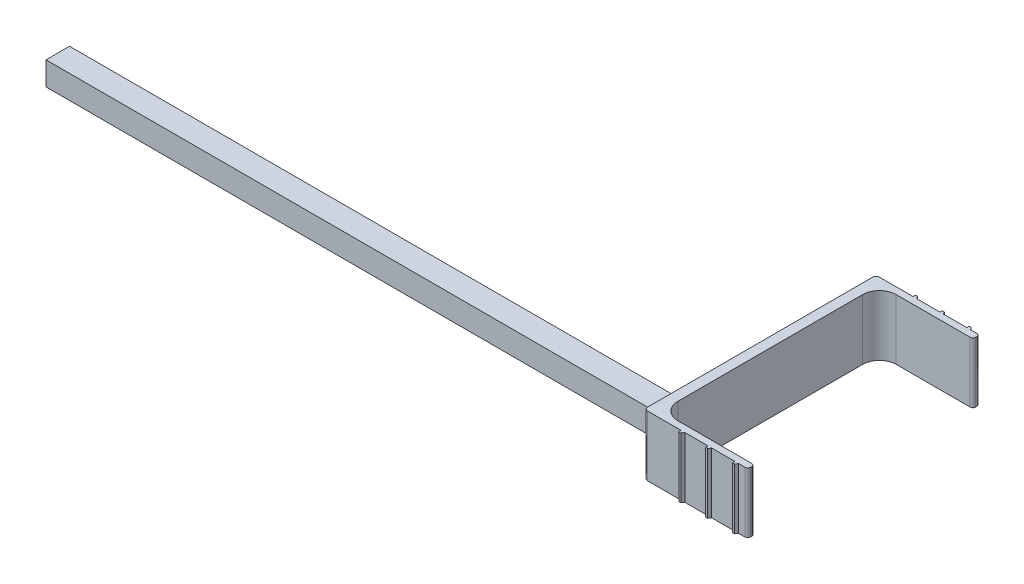
SolidWorks part; units mm, degrees
ref_plane "Front Plane" through (0, 0, 0) normal (0, 0, 1) x (1, 0, 0)
ref_plane "Top Plane" through (0, 0, 0) normal (0, 1, 0) x (1, 0, 0)
ref_plane "Right Plane" through (0, 0, 0) normal (1, 0, 0) x (0, 0, -1)
sketch "Sketch1" plane through (0, 0, 0) normal (0, 1, 0) x (1, 0, 0)
  line L2 (7.0534, -34.5) -> (18.0534, -34.5)
  line L6 (10.0534, -32.5) -> (37.0534, -32.5)
  line L7 (37.8534, -33.3) -> (37.8534, -33.7)
  line L8 (10.0534, -32.5) -> (10.0534, 0)
  line L11 (26.0534, -35.2) -> (26.0534, -34.5)
  line L12 (18.6514, -35.2) -> (18.0534, -35.2)
  line L13 (18.6514, -35.2) -> (19.1514, -34.5)
  line L14 (18.0534, -35.2) -> (18.0534, -34.5)
  line L15 (26.6514, -35.2) -> (26.0534, -35.2)
  line L16 (26.6514, -35.2) -> (27.1514, -34.5)
  line L17 (34.0534, -35.2) -> (34.0534, -34.5)
  line L18 (34.6514, -35.2) -> (34.0534, -35.2)
  line L19 (34.6514, -35.2) -> (35.1514, -34.5)
  line L65 (19.1514, -34.5) -> (26.0534, -34.5)
  line L66 (27.1514, -34.5) -> (34.0534, -34.5)
  line L67 (35.1514, -34.5) -> (37.0534, -34.5)
  line L179 (7.0534, 0) -> (10.0534, 0)
  line L180 (7.0534, 0) -> (7.0534, -34.5)
  line L181 (7.0534, -22.5) -> (-182.9466, -22.5)
  line L182 (7.0534, -15.5) -> (-182.9466, -15.5)
  line L183 (-182.9466, -22.5) -> (-182.9466, -15.5)
  line L184 (7.0534, -22.5) -> (7.0534, -15.5)
  arc A2 (37.0534, -34.5) -> (37.8534, -33.7) centre (37.0534, -33.7) ccw
  arc A3 (37.0534, -32.5) -> (37.8534, -33.3) centre (37.0534, -33.3) cw
  dimension "D3" = 0.8
  dimension "D7" = 11
  dimension "D11" = 190
  dimension "D20" = 8
  dimension "D4" = 2
  dimension "D5" = 3
  dimension "D6" = 34.5
  dimension "D8" = 7
  dimension "D9" = 30
  dimension "D10" = 12
  dimension "D14" = 0.7
  dimension "D15" = 1.098
  dimension "D17" = 0.5
  dimension "D18" = 0.598
  dimension "D19" = 3
extrude "Boss-Extrude1" add sketch "Sketch1" along normal blind 18 contours A3 L6 L8 L179 L180 L2 L14 L12 L13 L65 L11 L15 L16 L66 L17 L18 L19 L67 A2 L7 region at (7.5211, 0, 28.5)
fillet "Fillet1" radius 5 1 edges at (10.0534, 9, 32.5)
fillet "Fillet2" radius 1 1 edges at (7.0534, 9, 34.5)
mirror "Mirror1" about plane through (0, 18, 0) normal (0, 0, -1) of bodies 101
extrude "Boss-Extrude2" add sketch "Sketch1<3>" along normal blind 7 contours L183 L181 L180 L182 region at (-87.9466, 0, 19)
sketch "Sketch1<3>" plane through (0, 0, 0) normal (0, 1, 0) x (1, 0, 0) same geometry as "Sketch1"
fillet "Fillet3" radius 10 3 edges at (7.0534, 3.5, 22.5) (7.0534, 3.5, 15.5) (7.0534, 7, 19)
